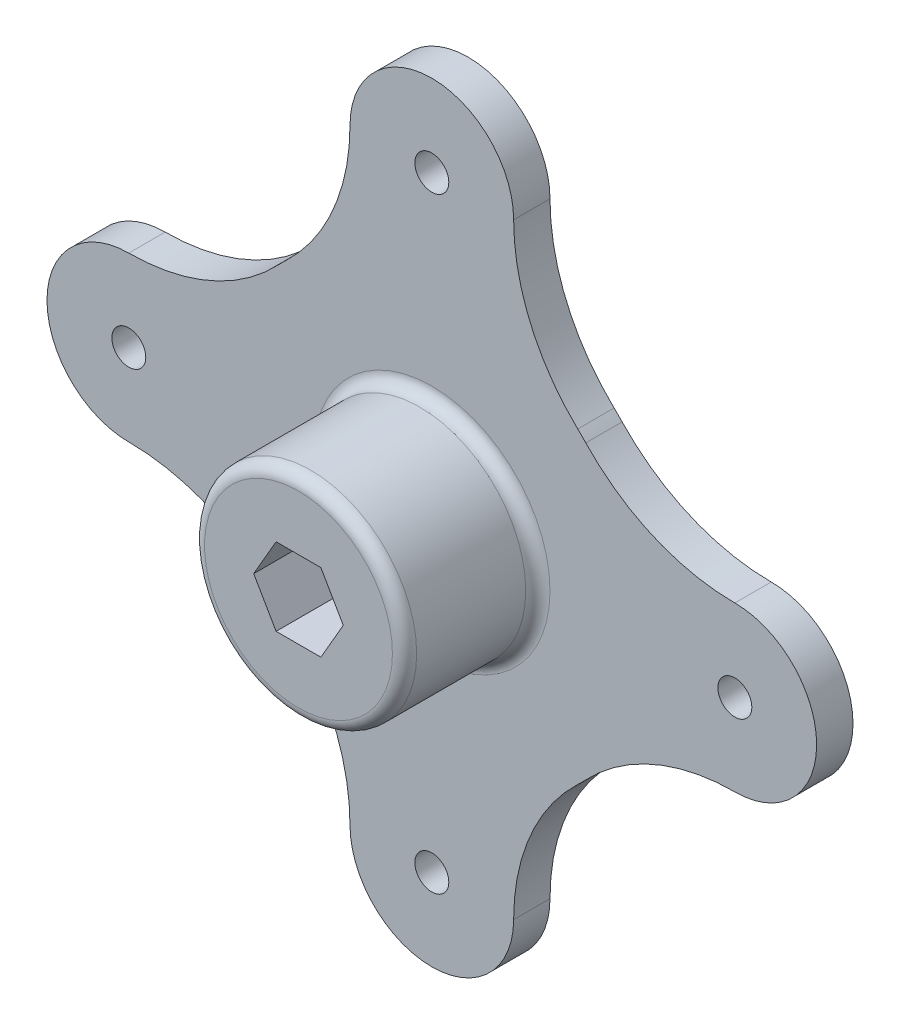
SolidWorks part; units mm, degrees
ref_plane "Front Plane" through (0, 0, 0) normal (0, 0, 1) x (1, 0, 0)
ref_plane "Top Plane" through (0, 0, 0) normal (0, 1, 0) x (1, 0, 0)
ref_plane "Right Plane" through (0, 0, 0) normal (1, 0, 0) x (0, 0, -1)
sketch "Sketch1" plane through (0, 0, 0) normal (0, 0, 1) x (1, 0, 0)
  line L1 (3.695, 0) -> (1.8475, 3.2)
  line L2 (1.8475, 3.2) -> (-1.8475, 3.2)
  line L3 (-1.8475, 3.2) -> (-3.695, 0)
  line L4 (-3.695, 0) -> (-1.8475, -3.2)
  line L5 (-1.8475, -3.2) -> (1.8475, -3.2)
  line L6 (1.8475, -3.2) -> (3.695, 0)
  circle A0 centre (0, 0) radius 3.2 construction
  dimension "D1" = 6.4
sketch "Sketch2" plane through (0, 0, 0) normal (0, 0, 1) x (1, 0, 0)
  circle A0 centre (0, 0) radius 8.75
  dimension "D1" = 17.5
extrude "Boss-Extrude1" add sketch "Sketch2" along normal blind 14
sketch "Sketch3" plane through (0, 0, 0) normal (0, 0, 1) x (1, 0, 0)
  circle A0 centre (0, 25) radius 1.4
  arc A1 (6.75, 25) -> (-6.75, 25) centre (0, 25) ccw
  circle A2 centre (0, 0) radius 17.5 construction
  arc A3 (-6.75, 25) -> (-12.0384, 12.7015) centre (-23.6948, 25) cw
  arc A4 (6.75, 25) -> (12.0384, 12.7015) centre (23.6948, 25) ccw
  arc A5 (-6.75, 25) -> (6.75, 25) centre (0, 25) ccw construction
  arc A6 (-25, 6.75) -> (-12.7015, 12.0384) centre (-25, 23.6948) ccw
  circle A7 centre (-25, 0) radius 1.4
  arc A8 (-25, 6.75) -> (-25, -6.75) centre (-25, 0) ccw
  arc A9 (-25, -6.75) -> (-12.7015, -12.0384) centre (-25, -23.6948) cw
  arc A10 (-6.75, -25) -> (-12.0384, -12.7015) centre (-23.6948, -25) ccw
  circle A11 centre (0, -25) radius 1.4
  arc A12 (-6.75, -25) -> (6.75, -25) centre (0, -25) ccw
  arc A13 (6.75, -25) -> (12.0384, -12.7015) centre (23.6948, -25) cw
  arc A14 (25, -6.75) -> (12.7015, -12.0384) centre (25, -23.6948) ccw
  circle A15 centre (25, 0) radius 1.4
  arc A16 (25, -6.75) -> (25, 6.75) centre (25, 0) ccw
  arc A17 (25, 6.75) -> (12.7015, 12.0384) centre (25, 23.6948) cw
  arc A18 (-12.7015, 12.0384) -> (-12.0384, 12.7015) centre (0, 0) cw
  arc A19 (12.0384, 12.7015) -> (12.7015, 12.0384) centre (0, 0) cw
  arc A20 (12.7015, -12.0384) -> (12.0384, -12.7015) centre (0, 0) cw
  arc A21 (-12.0384, -12.7015) -> (-12.7015, -12.0384) centre (0, 0) cw
  point P38 (0, 0)
  dimension "D1" = 35
  dimension "D2" = 13.5
  dimension "D4" = 2.8
  dimension "D3" = 25
  dimension "D5" = 4
extrude "Boss-Extrude2" add sketch "Sketch3" along normal blind 3 contours A21 A10 A12 A13 A20 A14 A16 A17 A19 A4 A1 A3 A18 A6 A8 A9 A15 A11 A7 A0 region at (0, 0, 0)
fillet "Fillet1" radius 1 2 edges at (8.75, 0, 3) (8.75, 0, 14)
extrude "Cut-Extrude2" cut sketch "Sketch1" along normal up to next
